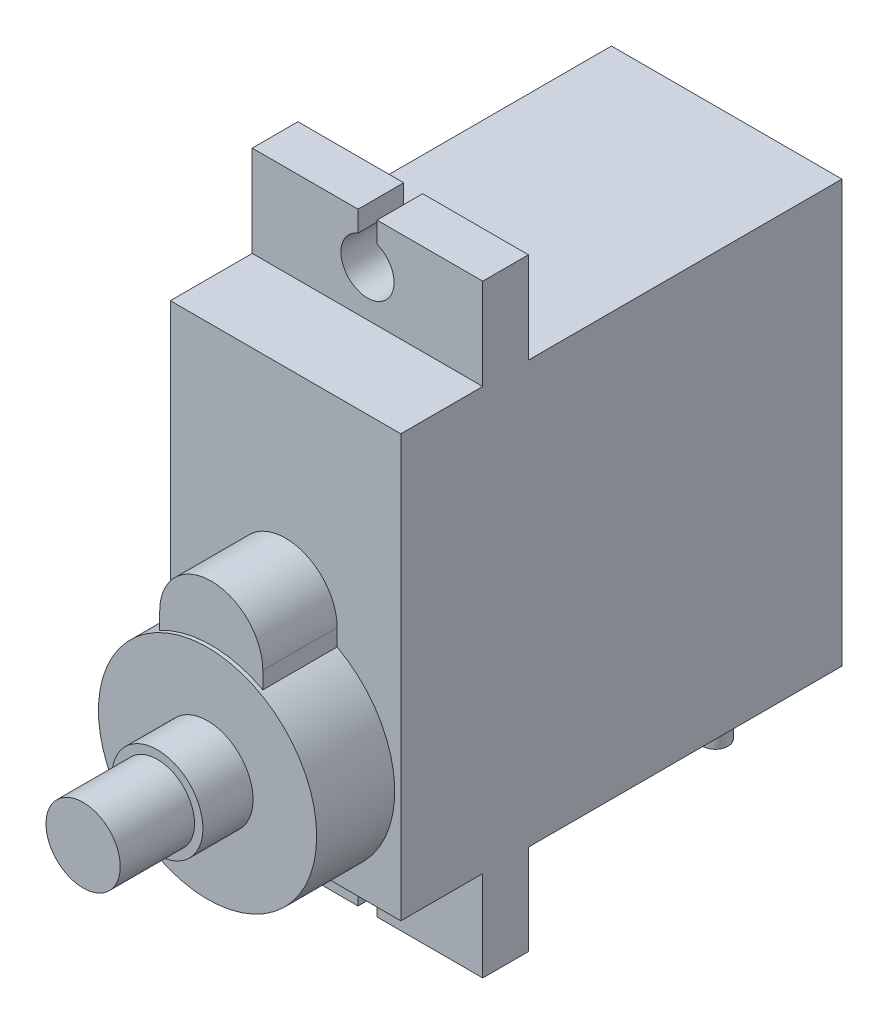
SolidWorks part; units mm, degrees
ref_plane "Front" through (0, 0, 0) normal (0, 0, 1) x (1, 0, 0)
ref_plane "Top" through (0, 0, 0) normal (0, 1, 0) x (1, 0, 0)
ref_plane "Right" through (0, 0, 0) normal (1, 0, 0) x (0, 0, -1)
sketch "Sketch1" plane through (0, 0, 0) normal (0, 1, 0) x (1, 0, 0)
  line L0 (0, 0) -> (12.41, 0)
  line L1 (12.41, 0) -> (12.41, 23.75)
  line L2 (12.41, 23.75) -> (0, 23.75)
  line L3 (0, 23.75) -> (0, 0)
  dimension "D1" = 23.75
  dimension "D2" = 12.41
extrude "Boss-Extrude1" add sketch "Sketch1" along normal blind 22.71
sketch "Sketch2" plane through (0, 0, 0) normal (0, 0, 1) x (1, 0, 0)
  line L0 (6.205, 22.71) -> (6.205, 0) construction
  line L1 (0, 22.71) -> (12.41, 22.71) construction
  line L2 (0, 0) -> (12.41, 0) construction
  circle A0 centre (6.205, 5.875) radius 5.875
  dimension "D1" = 11.75
  dimension "D2" = 5.875
extrude "Boss-Extrude3" add sketch "Sketch2" along normal blind 4.2
sketch "Sketch4" plane through (0, 0, 0) normal (0, 0, 1) x (1, 0, 0)
  line L0 (6.205, 11.5321) -> (6.205, 22.71) construction
  line L1 (0, 22.71) -> (12.41, 22.71) construction
  line L2 (0, 14.74) -> (12.41, 14.74) construction
  line L3 (0, 22.71) -> (0, 0) construction
  line L4 (12.41, 22.71) -> (12.41, 0) construction
  line L5 (3.43, 11.965) -> (3.43, 11.0533)
  line L6 (3.43, 11.0533) -> (8.98, 11.0533)
  line L7 (8.98, 11.0533) -> (8.98, 11.965)
  circle A0 centre (6.205, 5.875) radius 5.875 construction
  arc A1 (8.98, 11.965) -> (3.43, 11.965) centre (6.205, 11.965) ccw
  circle A2 centre (6.205, 5.875) radius 5.875 construction
  dimension "D2" = 5.55
  dimension "D1" = 14.74
extrude "Boss-Extrude4" add sketch "Sketch4" along normal blind 4
sketch "Sketch6" plane through (0, 0, 0) normal (0, -1, 0) x (1, 0, 0)
  line L0 (0, -4.41) -> (12.41, -4.41)
  line L1 (0, -23.75) -> (0, 0) construction
  line L2 (12.41, 0) -> (12.41, -23.75) construction
  line L3 (12.41, -4.41) -> (12.41, -6.87)
  line L4 (12.41, -6.87) -> (0, -6.87)
  line L5 (0, -6.87) -> (0, -4.41)
  line L6 (0, 0) -> (6.205, 0) construction
  dimension "D1" = 2.46
  dimension "D2" = 4.41
extrude "Boss-Extrude5" add sketch "Sketch6" along normal blind 4.87 and the other way blind 27.62
sketch "Sketch8" plane through (0, 0, -4.41) normal (0, 0, 1) x (1, 0, 0)
  line L0 (6.205, -4.87) -> (6.205, 27.62) construction
  line L1 (12.41, -4.87) -> (0, -4.87) construction
  line L3 (0, 22.71) -> (12.41, 27.62) construction
  line L4 (6.205, 11.375) -> (12.41, 11.375) construction
  line L5 (12.41, 22.71) -> (12.41, 0) construction
  line L6 (0, -4.87) -> (12.41, 0) construction
  line L10 (12.41, 27.62) -> (0, 27.62) construction
  circle A0 centre (6.205, 25.165) radius 1.43
  circle A1 centre (6.205, -2.415) radius 1.43
  dimension "D1" = 2.86
extrude "Cut-Extrude1" cut sketch "Sketch8" against normal through all
sketch "Sketch9" plane through (0, 0, -4.41) normal (0, 0, 1) x (1, 0, 0)
  line L0 (6.205, 27.62) -> (6.205, 25.165) construction
  line L2 (12.41, -4.87) -> (0, -4.87) construction
  line L3 (5.695, 27.62) -> (5.695, 25.165)
  line L4 (6.715, 27.62) -> (6.715, 25.165)
  line L5 (5.695, 25.165) -> (6.715, 25.165)
  line L6 (5.695, -2.415) -> (6.715, -2.415)
  line L7 (5.695, -2.415) -> (5.695, -4.87)
  line L8 (5.695, 27.62) -> (5.695, -4.87) construction
  line L9 (6.205, -2.415) -> (6.205, -4.87) construction
  line L10 (6.205, 27.62) -> (6.205, -4.87) construction
  line L11 (6.715, -2.415) -> (6.715, -4.87)
  line L12 (6.715, 27.62) -> (6.715, -4.87) construction
  line L13 (5.695, -4.87) -> (6.715, -4.87)
  line L14 (5.695, 27.62) -> (6.715, 27.62)
  line L15 (12.41, 27.62) -> (0, 27.62) construction
  dimension "D1" = 0.51
  dimension "D2" = 0.51
extrude "Cut-Extrude2" cut sketch "Sketch9" against normal through all
sketch "Sketch10" plane through (0, 0, 4.2) normal (0, 0, 1) x (1, 0, 0)
  circle A0 centre (6.205, 5.875) radius 2.45
  circle A1 centre (6.205, 5.875) radius 0.885
  dimension "D1" = 4.9
  dimension "D2" = 1.77
extrude "Boss-Extrude7" add sketch "Sketch10" along normal blind 2.7
sketch "Sketch12" plane through (0, 0, 0) normal (0, -1, 0) x (1, 0, 0)
  line L0 (6.205, -23.75) -> (6.205, 0) construction
  line L1 (12.41, -23.75) -> (0, -23.75) construction
  arc A0 (5.61, -22.2894) -> (6.8, -22.2894) centre (6.205, -21.95) ccw
  arc A2 (5.61, -21.6106) -> (5.61, -22.2894) centre (5.015, -21.95) ccw
  arc A3 (6.8, -22.2894) -> (6.8, -21.6106) centre (7.395, -21.95) ccw
  arc A4 (6.8, -21.6106) -> (5.61, -21.6106) centre (6.205, -21.95) ccw
  point P5 (6.205, -21.95)
  dimension "D3" = 1.8
  dimension "D1" = 2
  dimension "D2" = 2
extrude "Boss-Extrude8" add sketch "Sketch12" along normal blind 5
ref_axis "servoAxis" through (6.205, 5.875, 10.5376) along (0, 0, -1)
sketch "Sketch13" plane through (0, 0, 6.9) normal (0, 0, 1) x (1, 0, 0)
  circle A0 centre (6.205, 5.875) radius 2
  circle A1 centre (6.205, 5.875) radius 2.45 construction
  dimension "D1" = 4
extrude "Boss-Extrude9" add sketch "Sketch13" along normal blind 4
sketch "Sketch14" plane through (0, 0, 0) normal (-1, 0, 0) x (0, 0, 1)
  line L0 (10.9, 5.875) -> (-44.4884, 5.875)
  line L1 (10.9, 3.875) -> (10.9, 7.875) construction
  point P4 (-44.4884, 5.875)
